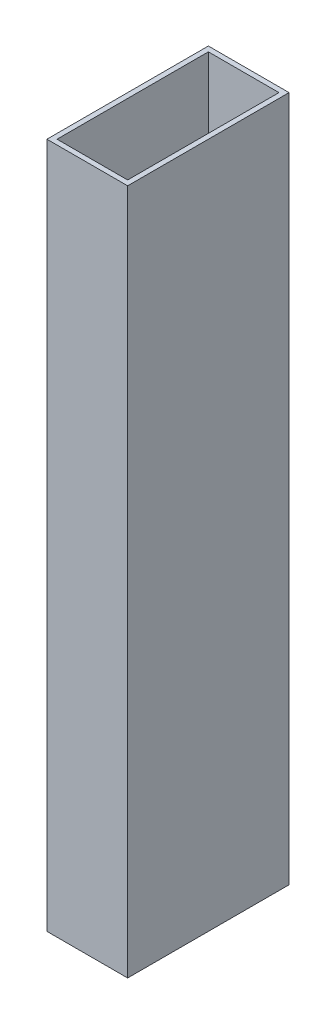
SolidWorks part; units mm, degrees
material "6061-T6 (SS)"
ref_plane "Front" through (0, 0, 0) normal (0, 0, 1) x (1, 0, 0)
ref_plane "Top" through (0, 0, 0) normal (0, 1, 0) x (1, 0, 0)
ref_plane "Right" through (0, 0, 0) normal (1, 0, 0) x (0, 0, -1)
sketch "Sketch1" plane through (0, 0, 0) normal (0, 1, 0) x (1, 0, 0)
  line L1 (12.7, 25.4) -> (-12.7, 25.4)
  line L2 (12.7, 25.4) -> (12.7, -25.4)
  line L3 (12.7, -25.4) -> (-12.7, -25.4)
  line L4 (-12.7, 25.4) -> (-12.7, -25.4)
  line L5 (12.7, 25.4) -> (-12.7, -25.4) construction
  line L6 (12.7, -25.4) -> (-12.7, 25.4) construction
  point P0 (0, 0)
  dimension "D1" = 25.4
  dimension "D2" = 50.8
extrude "Extrude-Thin1" add sketch "Sketch1" along normal up to surface (215.9 mm away) thin thin type one direction reverse wall 1.5875
